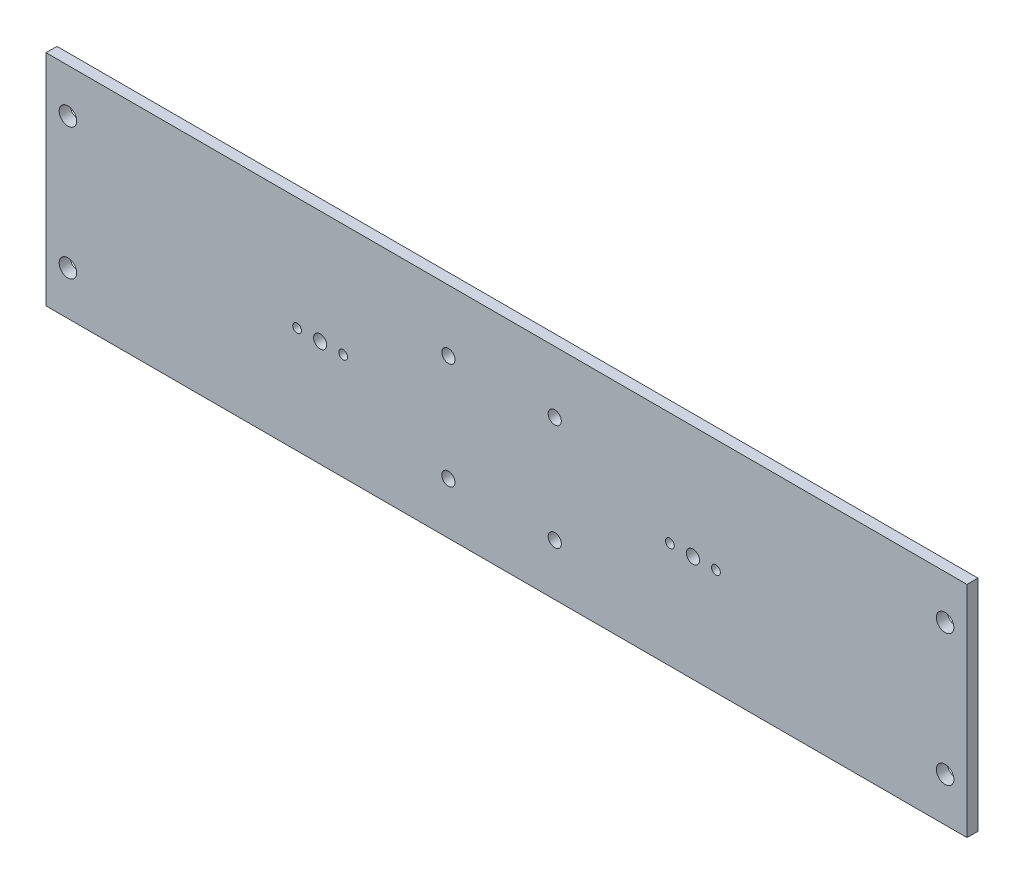
SolidWorks part; units mm, degrees
ref_plane "Front Plane" through (0, 0, 0) normal (0, 0, 1) x (1, 0, 0)
ref_plane "Top Plane" through (0, 0, 0) normal (0, 1, 0) x (1, 0, 0)
ref_plane "Right Plane" through (0, 0, 0) normal (1, 0, 0) x (0, 0, -1)
sketch "Sketch2" plane through (0, 0, 0) normal (0, 0, 1) x (1, 0, 0)
  line L1 (0, 100) -> (420, 100)
  line L2 (0, 100) -> (0, 0)
  line L3 (0, 0) -> (420, 0)
  line L4 (420, 100) -> (420, 0)
  point P4 (0, 0)
  dimension "D1" = 100
  dimension "D2" = 420
extrude "Boss-Extrude1" add sketch "Sketch2" along normal blind 5
sketch "Sketch8" plane through (0, 0, 5) normal (0, 0, 1) x (1, 0, 0)
  circle A0 centre (183.5, 23.5) radius 3
  circle A2 centre (183.5, 72) radius 3
  circle A3 centre (232, 72) radius 3
  circle A4 centre (232, 23.5) radius 3
  dimension "D1" = 2
  dimension "D2" = 2
extrude "Cut-Extrude2" cut sketch "Sketch8" against normal through all
sketch "Sketch9" plane through (0, 0, 5) normal (0, 0, 1) x (1, 0, 0)
  circle A0 centre (125, 48.5) radius 3
  circle A1 centre (135.5, 48.5) radius 2
  circle A2 centre (114.5, 48.5) radius 2
  circle A3 centre (295, 48.5) radius 3
  circle A4 centre (305.5, 48.5) radius 2
  circle A5 centre (284.5, 48.5) radius 2
  dimension "D1" = 2
extrude "Cut-Extrude3" cut sketch "Sketch9" against normal through all
sketch "Sketch11" plane through (0, 0, 5) normal (0, 0, 1) x (1, 0, 0)
  circle A0 centre (10, 80) radius 4
  circle A1 centre (10, 20) radius 4
  circle A2 centre (410, 20) radius 4
  circle A3 centre (410, 80) radius 4
  dimension "D1" = 2
  dimension "D2" = 60
  dimension "D3" = 2
extrude "Cut-Extrude4" cut sketch "Sketch11" against normal through all
